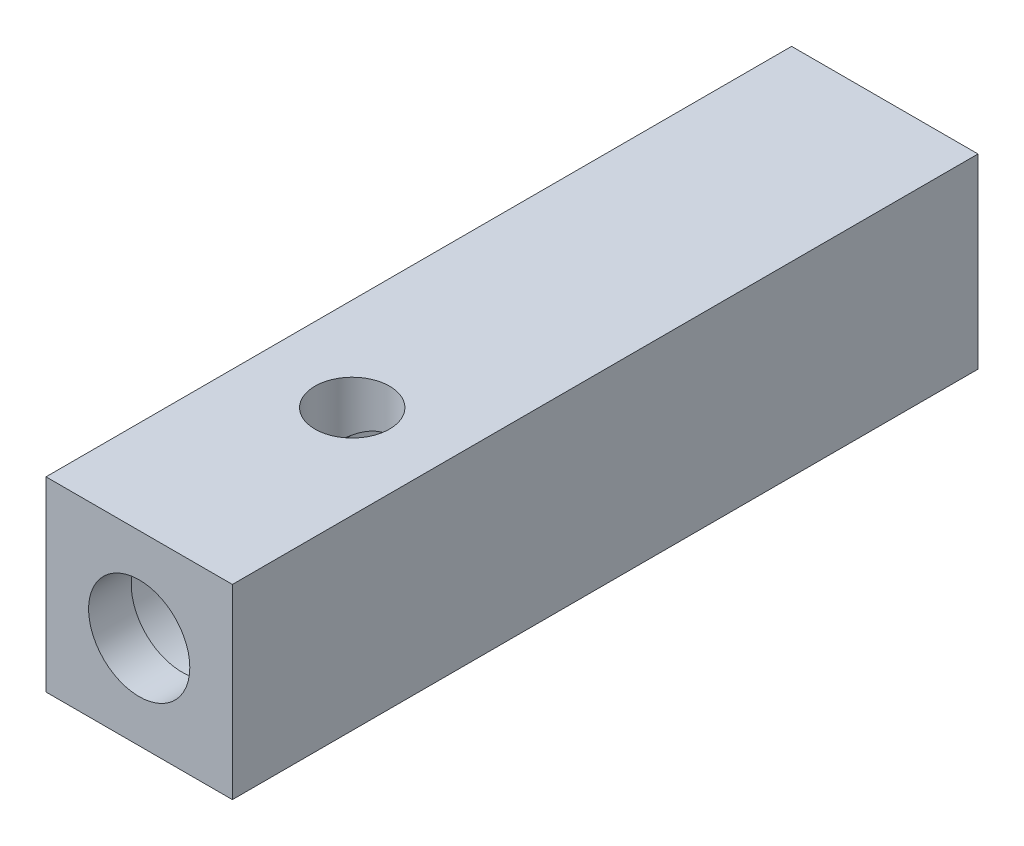
SolidWorks part; units mm, degrees
ref_plane "Front Plane" through (0, 0, 0) normal (0, 0, 1) x (1, 0, 0)
ref_plane "Top Plane" through (0, 0, 0) normal (0, 1, 0) x (1, 0, 0)
ref_plane "Right Plane" through (0, 0, 0) normal (1, 0, 0) x (0, 0, -1)
sketch "Sketch1" plane through (0, 0, 0) normal (0, 0, 1) x (1, 0, 0)
  line L1 (-9.5, 7.8952) -> (8, 7.8952)
  line L2 (-9.5, 7.8952) -> (-9.5, -9.6048)
  line L3 (-9.5, -9.6048) -> (8, -9.6048)
  line L4 (8, 7.8952) -> (8, -9.6048)
  dimension "D1" = 17.5
  dimension "D2" = 17.5
extrude "Boss-Extrude1" add sketch "Sketch1" along normal blind 70 from offset 20 offset against normal yes
sketch "Sketch2" plane through (0, 0, -20) normal (0, 0, -1) x (-1, 0, 0)
  line L1 (-8, -9.6048) -> (-8, 7.8952) construction
  line L5 (9.5, -9.6048) -> (-8, -9.6048) construction
  circle A0 centre (0.75, -0.8548) radius 4.75
  dimension "D1" = 9.5
  dimension "D2" = 8.75
  dimension "D3" = 8.75
extrude "Cut-Extrude1" cut sketch "Sketch2" against normal blind 150
sketch "Sketch3" plane through (0, 7.8952, 0) normal (0, 1, 0) x (1, 0, 0)
  line L1 (-9.5, -50) -> (-9.5, 20) construction
  line L2 (8, -50) -> (-9.5, -50) construction
  circle A0 centre (-0.75, -30) radius 3.5
  point P4 (0, 0)
  point P6 (-0.7913, -33.4998)
  point P7 (0.2383, -31.9776)
  point P11 (-0.75, -30)
  dimension "D3" = 20
  dimension "D1" = 7
  dimension "D2" = 8.75
extrude "Cut-Extrude6" cut sketch "Sketch3" against normal blind 25
sketch "Sketch4" plane through (0, 0, 50) normal (0, 0, 1) x (1, 0, 0)
  line L0 (8, 7.8952) -> (-9.5, 7.8952) construction
  line L1 (-9.5, 7.8952) -> (-9.5, -9.6048) construction
  line L2 (-0.75, -0.8548) -> (4.1997, -5.8046)
  line L3 (-0.75, -0.8548) -> (-5.6997, 4.0949)
  line L4 (-0.75, -0.8548) -> (-7.75, -0.8548)
  line L6 (-7.75, -0.8548) -> (-0.75, -0.8548)
  line L7 (-0.75, -0.8548) -> (6.25, -0.8548)
  line L8 (1.9288, -7.322) -> (-3.4288, 5.6123)
  line L9 (3.0809, -6.7135) -> (-4.5809, 5.0038)
  arc A2 (6.25, -0.8548) -> (-5.6997, 4.0949) centre (-0.75, -0.8548) ccw
  arc A3 (-7.75, -0.8548) -> (4.1997, -5.8046) centre (-0.75, -0.8548) ccw
  point P5 (-0.75, 7.8952)
  circle M5 centre (-0.75, -0.8548) radius 4.75
  dimension "D1" = 14
  dimension "D2" = 8.75
  dimension "D3" = 8.75
sketch "Sketch6" plane through (0, 0, 50) normal (0, 0, 1) x (1, 0, 0)
  line L0 (-7.2883, 1.6452) -> (5.7883, 1.6452)
  line L1 (5.7883, -3.3548) -> (-7.2883, -3.3548)
  arc A0 (-7.2883, 1.6452) -> (-7.2883, -3.3548) centre (-0.75, -0.8548) ccw
  arc A1 (5.7883, -3.3548) -> (5.7883, 1.6452) centre (-0.75, -0.8548) ccw
  dimension "D1" = 14
  dimension "D2" = 5
  dimension "D3" = 2.5
extrude "Cut-Extrude9" cut sketch "Sketch6" against normal up to surface (70 mm away) from offset 4 up to face at (-5.5, -0.8548, -20) offset against normal yes
extrude "Cut-Extrude13" cut sketch "Sketch4" against normal blind 5 from offset 4 contours L8 A3 L9 M5 | L4 A3 L8 M5 | L8 A2 L9 M5 | L7 A2 L8 M5 region at (-3.5481, -5.0426, 50) region at (2.0481, 3.3329, 50) region at (2.0232, -6.1057, 50) region at (-3.5232, 4.396, 50) offset against normal yes
